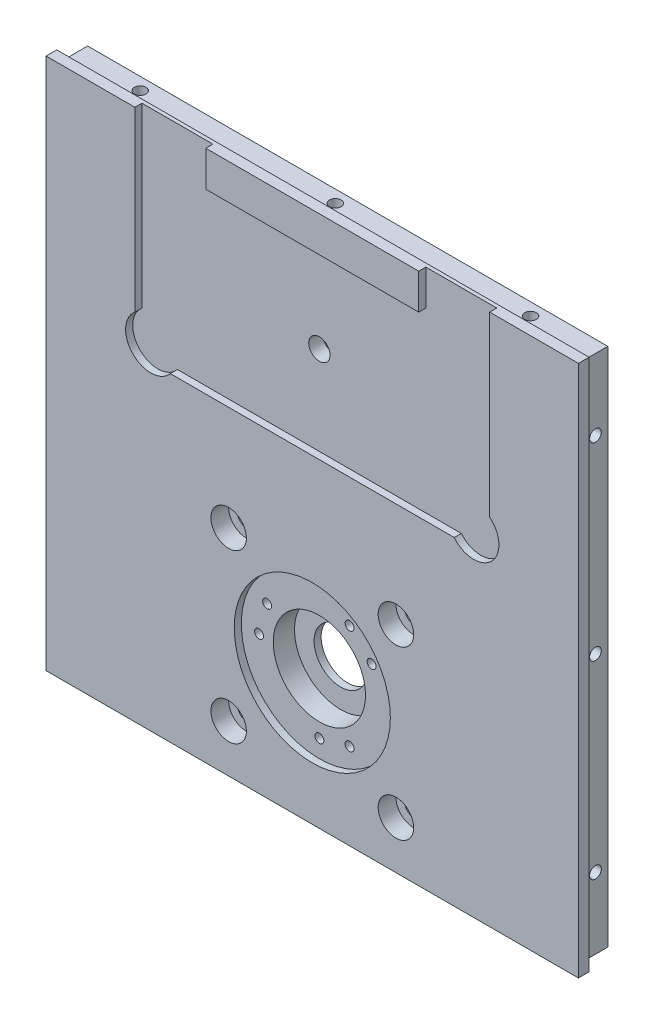
SolidWorks part; units mm, degrees
ref_plane "Спереди" through (0, 0, 0) normal (0, 0, 1) x (1, 0, 0)
ref_plane "Сверху" through (0, 0, 0) normal (0, 1, 0) x (1, 0, 0)
ref_plane "Справа" through (0, 0, 0) normal (1, 0, 0) x (0, 0, -1)
sketch "Эскиз1" plane through (0, 0, 0) normal (0, 0, 1) x (1, 0, 0)
  line L1 (0, 0) -> (150, 0)
  line L2 (0, 0) -> (0, 150)
  line L3 (0, 150) -> (150, 150)
  line L4 (150, 0) -> (150, 150)
  dimension "D1" = 150
  dimension "D2" = 150
extrude "Бобышка-Вытянуть1" add sketch "Эскиз1" along normal blind 10
sketch "Эскиз2" plane through (0, 0, 10) normal (0, 0, 1) x (1, 0, 0)
  line L0 (0, 0) -> (150, 0) construction
  circle A0 centre (75, 37) radius 13
  point P4 (75, 0)
  dimension "D3" = 26
  dimension "D1" = 0
  dimension "D2" = 37
extrude "Вырез-Вытянуть1" cut sketch "Эскиз2" against normal blind 8
sketch "Эскиз3" plane through (0, 0, 10) normal (0, 0, 1) x (1, 0, 0)
  circle A0 centre (75, 37) radius 7.5
  dimension "D1" = 15
extrude "Вырез-Вытянуть3" cut sketch "Эскиз3" against normal through all
sketch "Эскиз4" plane through (0, 0, 10) normal (0, 0, 1) x (1, 0, 0)
  circle A0 centre (75, 37) radius 22
  dimension "D1" = 44
extrude "Вырез-Вытянуть4" cut sketch "Эскиз4" against normal blind 2
sketch "Эскиз5" plane through (0, 0, 10) normal (0, 0, 1) x (1, 0, 0)
  circle A0 centre (51.43, 13.43) radius 2.5
  circle A1 centre (75, 37) radius 7.5 construction
  circle A2 centre (98.57, 13.43) radius 2.5
  circle A3 centre (98.57, 60.57) radius 2.5
  circle A4 centre (51.43, 60.57) radius 2.5
  dimension "D1" = 5
  dimension "D2" = 23.57
  dimension "D3" = 23.57
  dimension "D4" = 2
  dimension "D5" = 2
extrude "Вырез-Вытянуть5" cut sketch "Эскиз5" against normal through all
sketch "Эскиз6" plane through (0, 0, 0) normal (0, 0, -1) x (-1, 0, 0)
  line L0 (0, 150) -> (0, 0) construction
  line L1 (-148.3, 148.3) -> (-1.7, 148.3)
  line L2 (-148.3, 148.3) -> (-148.3, 1.7)
  line L3 (-148.3, 1.7) -> (-1.7, 1.7)
  line L4 (-1.7, 148.3) -> (-1.7, 1.7)
  line L5 (-150, 150) -> (0, 150) construction
  line L6 (-150, 0) -> (-150, 150) construction
  line L7 (0, 0) -> (-150, 0) construction
  line L9 (-159.0813, 154.0692) -> (4.376, 154.0692)
  line L10 (-159.0813, 154.0692) -> (-159.0813, -3.2509)
  line L11 (-159.0813, -3.2509) -> (4.376, -3.2509)
  line L12 (4.376, 154.0692) -> (4.376, -3.2509)
  dimension "D1" = 1.7
  dimension "D2" = 1.7
  dimension "D3" = 1.7
  dimension "D4" = 1.7
extrude "Вырез-Вытянуть6" cut sketch "Эскиз6" against normal blind 7
sketch "Эскиз7" plane through (0, 1.7, 0) normal (0, -1, 0) x (1, 0, 0)
  line L1 (0, 10) -> (0, 7) construction
  line L2 (148.3, 7) -> (1.7, 7) construction
  circle A0 centre (20, 3.5) radius 1.65
  circle A1 centre (75, 3.5) radius 1.65
  circle A2 centre (130, 3.5) radius 1.65
  dimension "D4" = 3.3
  dimension "D1" = 3.5
  dimension "D2" = 20
  dimension "D3" = 3
extrude "Вырез-Вытянуть7" cut sketch "Эскиз7" against normal blind 15
sketch "Эскиз8" plane through (0, 148.3, 0) normal (0, 1, 0) x (1, 0, 0)
  circle A0 centre (20, -3.5) radius 1.65
  circle A1 centre (75, -3.5) radius 1.65
  circle A2 centre (130, -3.5) radius 1.65
  circle A3 centre (20, -3.5) radius 1.65 construction
extrude "Вырез-Вытянуть8" cut sketch "Эскиз8" against normal blind 15
sketch "Эскиз9" plane through (148.3, 0, 0) normal (1, 0, 0) x (0, 0, -1)
  line L0 (0, 148.3) -> (0, 1.7) construction
  line L1 (-7, 1.7) -> (0, 1.7) construction
  line L2 (-7, 148.3) -> (0, 148.3) construction
  line L3 (-7, 148.3) -> (-7, 1.7) construction
  circle A0 centre (-3.5, 21.7) radius 1.65
  circle A1 centre (-3.5, 128.3) radius 1.65
  circle A2 centre (-3.5, 75) radius 1.65
  point P11 (0, 75)
  dimension "D1" = 3.3
  dimension "D2" = 3.5
  dimension "D3" = 20
  dimension "D4" = 20
  dimension "D5" = 0
extrude "Вырез-Вытянуть9" cut sketch "Эскиз9" against normal blind 15
sketch "Эскиз10" plane through (1.7, 0, 0) normal (-1, 0, 0) x (0, 0, 1)
  circle A0 centre (3.5, 128.3) radius 1.65
  circle A1 centre (3.5, 75) radius 1.65
  circle A2 centre (3.5, 21.7) radius 1.65
  circle A3 centre (3.5, 128.3) radius 1.65 construction
extrude "Вырез-Вытянуть10" cut sketch "Эскиз10" against normal blind 15
sketch "Эскиз12" plane through (0, 0, 10) normal (0, 0, 1) x (1, 0, 0)
  line L0 (75, 37) -> (89.7224, 45.5) construction
  line L1 (75, 37) -> (83.5, 22.2776) construction
  circle A0 centre (75, 20) radius 1.25
  circle A1 centre (75, 37) radius 7.5 construction
  circle A2 centre (60.2776, 45.5) radius 1.25
  circle A3 centre (89.7224, 45.5) radius 1.25
  circle A7 centre (58, 37) radius 1.25
  circle A8 centre (83.5, 22.2776) radius 1.25
  circle A9 centre (83.5, 51.7224) radius 1.25
  point P10 (75, 37)
  dimension "D1" = 2.5
  dimension "D2" = 0
  dimension "D3" = 17
  dimension "D6" = 90
  dimension "D4" = 3
  dimension "D5" = 2
extrude "Вырез-Вытянуть11" cut sketch "Эскиз12" against normal through all
sketch "Эскиз14" plane through (0, 0, 10) normal (0, 0, 1) x (1, 0, 0)
  circle A0 centre (51.43, 13.43) radius 5
  circle A1 centre (98.57, 13.43) radius 5
  circle A2 centre (98.57, 60.57) radius 5
  circle A3 centre (51.43, 60.57) radius 5
  dimension "D1" = 10
  dimension "D2" = 2
  dimension "D3" = 2
extrude "Вырез-Вытянуть12" cut sketch "Эскиз14" against normal blind 5
sketch "Эскиз15" plane through (0, 0, 10) normal (0, 0, 1) x (1, 0, 0)
  line L0 (150, 150) -> (0, 150) construction
  line L1 (25, 140) -> (125, 140)
  line L2 (25, 140) -> (25, 90)
  line L3 (25, 90) -> (125, 90)
  line L4 (125, 140) -> (125, 90)
  point P4 (75, 140)
  point P7 (75, 150)
  dimension "D1" = 0
  dimension "D2" = 10
  dimension "D3" = 50
  dimension "D4" = 100
extrude "Вырез-Вытянуть13" cut sketch "Эскиз15" against normal blind 2
sketch "Эскиз16" plane through (0, 0, 10) normal (0, 0, 1) x (1, 0, 0)
  line L0 (25, 90) -> (125, 90) construction
  line L1 (25, 140) -> (25, 90) construction
  circle A0 centre (29.5, 94.5) radius 7.1
  circle A1 centre (120.5, 94.5) radius 7.1
  circle A4 centre (120.5, 135.5) radius 7.1 [skipped]
  circle A5 centre (29.5, 135.5) radius 7.1 [skipped]
  dimension "D1" = 14.2
  dimension "D2" = 4.5
  dimension "D3" = 4.5
  dimension "D4" = 2
  dimension "D5" = 2
extrude "Вырез-Вытянуть14" cut sketch "Эскиз16" against normal up to surface (2 mm away) up to face at (75, 115, 8)
sketch "Эскиз17" plane through (0, 0, 10) normal (0, 0, 1) x (1, 0, 0)
  line L0 (34.9918, 90) -> (115.0082, 90) construction
  line L1 (25, 140) -> (25, 99.9918) construction
  circle A0 centre (75, 115) radius 3
  dimension "D1" = 6
  dimension "D2" = 25
  dimension "D3" = 50
extrude "Вырез-Вытянуть15" cut sketch "Эскиз17" against normal through all
sketch "Эскиз18" plane through (0, 0, 10) normal (0, 0, 1) x (1, 0, 0)
  line L0 (150, 150) -> (0, 150) construction
  line L1 (25, 140) -> (45, 140)
  line L2 (25, 140) -> (25, 150)
  line L3 (25, 150) -> (45, 150)
  line L4 (45, 140) -> (45, 150)
  line L6 (125, 140) -> (105, 140)
  line L7 (125, 140) -> (125, 150)
  line L8 (125, 150) -> (105, 150)
  line L9 (105, 140) -> (105, 150)
  dimension "D1" = 20
extrude "Вырез-Вытянуть16" cut sketch "Эскиз18" against normal up to surface (2 mm away) up to face at (78, 115, 8)
sketch "Эскиз19" plane through (0, 0, 0) normal (0, 0, -1) x (-1, 0, 0)
  line L13 (-69.2265, 115) -> (-72.1132, 120)
  line L14 (-72.1132, 120) -> (-77.8868, 120)
  line L15 (-77.8868, 120) -> (-80.7735, 115)
  line L16 (-80.7735, 115) -> (-77.8868, 110)
  line L17 (-77.8868, 110) -> (-72.1132, 110)
  line L18 (-72.1132, 110) -> (-69.2265, 115)
  circle A0 centre (-75, 115) radius 5 construction
  dimension "D1" = 10
extrude "Вырез-Вытянуть17" cut sketch "Эскиз19" against normal blind 4
sketch "Эскиз20" plane through (0, 0, 0) normal (0, 0, -1) x (-1, 0, 0)
  circle A0 centre (-70.397, 115) radius 1.35
  circle A1 centre (-72.6985, 111.0137) radius 1.35
  circle A2 centre (-77.3015, 111.0137) radius 1.35
  circle A3 centre (-79.603, 115) radius 1.35
  circle A4 centre (-77.3015, 118.9863) radius 1.35
  circle A5 centre (-72.6985, 118.9863) radius 1.35
  point P15 (-75, 115)
  dimension "D1" = 2.7
  dimension "D2" = 6
extrude "Вырез-Вытянуть18" cut sketch "Эскиз20" against normal up to surface (4 mm away) up to face at (75, 115, 4)
